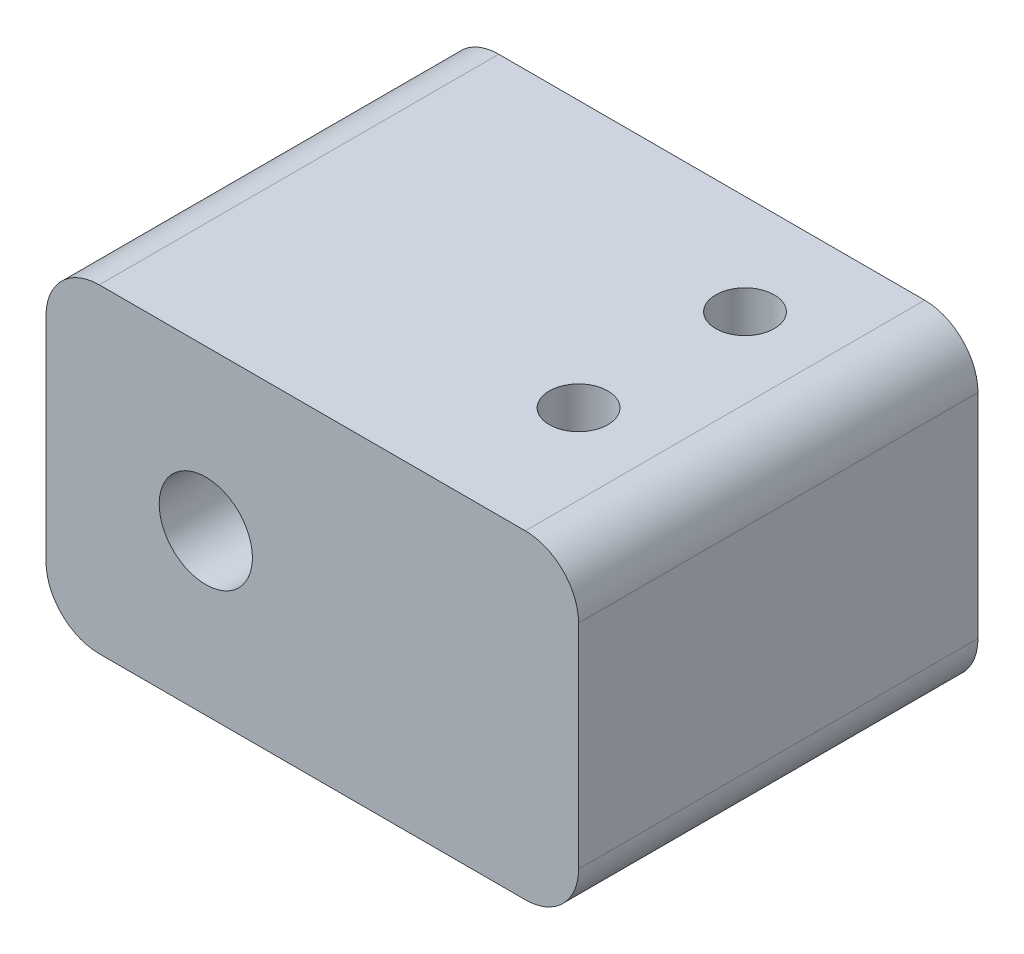
SolidWorks part; units mm, degrees
ref_plane "Front Plane" through (0, 0, 0) normal (0, 0, 1) x (1, 0, 0)
ref_plane "Top Plane" through (0, 0, 0) normal (0, 1, 0) x (1, 0, 0)
ref_plane "Right Plane" through (0, 0, 0) normal (1, 0, 0) x (0, 0, -1)
sketch "Sketch1" plane through (0, 0, 0) normal (0, 0, 1) x (1, 0, 0)
  circle A0 centre (0, 0) radius 1.25
  circle A1 centre (0, 0) radius 4.5
  dimension "D1" = 2.5
  dimension "D2" = 9
extrude "Boss-Extrude1" add sketch "Sketch1" along normal blind 8
sketch "Sketch2" plane through (0, 0, 0) normal (0, 0, -1) x (-1, 0, 0)
  circle A0 centre (0, 0) radius 1.25 construction
  circle A1 centre (0, 0) radius 4.5
  circle A2 centre (0, 0) radius 4.5
  circle A3 centre (0, 0) radius 1.25
  circle A4 centre (0, 0) radius 1.75
  circle M3 centre (0, 0) radius 1.25
  dimension "D2" = 3.5
  dimension "D1" = 0
extrude "Cut-Extrude1" cut sketch "Sketch2" against normal blind 4 contours A4 M3 region at (1.7005, 0, 0)
sketch "Sketch4" plane through (0, 0, 0) normal (0, 0, -1) x (-1, 0, 0)
  line L1 (3.25, -3.25) -> (-3.25, -3.25)
  line L2 (3.25, -3.25) -> (3.25, 3.25)
  line L3 (3.25, 3.25) -> (-3.25, 3.25)
  line L4 (-3.25, -3.25) -> (-3.25, 3.25)
  line L5 (0, 3.25) -> (0, -3.25) construction
  line L6 (3.25, 0) -> (-3.25, 0) construction
  line L7 (6, -6) -> (-6, -6)
  line L8 (6, -6) -> (6, 6)
  line L9 (6, 6) -> (-6, 6)
  line L10 (-6, -6) -> (-6, 6)
  line L11 (0, 6) -> (0, -6) construction
  line L12 (6, 0) -> (-6, 0) construction
  point P0 (0, 0)
  point P4 (0, 0)
  circle M5 centre (0, 0) radius 1.75
  circle M6 centre (0, 0) radius 4.5
  dimension "D1" = 6.5
  dimension "D2" = 6.5
  dimension "D3" = 12
  dimension "D4" = 12
extrude "Boss-Extrude2" add sketch "Sketch4" along normal blind 15
sketch "Sketch5" plane through (6, 0, 0) normal (1, 0, 0) x (0, 0, -1)
  line L4 (0, 6) -> (0, -6)
  line L5 (0, -6) -> (15, -6)
  line L6 (15, -6) -> (15, 6)
  line L7 (15, 6) -> (0, 6)
  line L8 (0, 6) -> (0, -6)
  line L9 (0, -6) -> (15, -6)
  line L10 (15, -6) -> (15, 6)
  line L11 (15, 6) -> (0, 6)
  dimension "D1" = 0
extrude "Boss-Extrude3" add sketch "Sketch5" along normal blind 8
sketch "Sketch6" plane through (0, 6, 0) normal (0, 1, 0) x (1, 0, 0)
  line L0 (4, 15) -> (4, 0) construction
  line L1 (4, 0) -> (14, 15) construction
  line L2 (9, 7.5) -> (9, 15) construction
  line L3 (9, 15) -> (9, 0) construction
  line L4 (-6, 0) -> (14, 0)
  line L5 (14, 0) -> (14, 15)
  line L6 (14, 15) -> (-6, 15)
  line L7 (-6, 15) -> (-6, 0)
  line L8 (-6, 0) -> (14, 0)
  line L9 (14, 0) -> (14, 15)
  line L10 (14, 15) -> (-6, 15)
  line L11 (-6, 15) -> (-6, 0)
  circle A0 centre (9, 11.25) radius 1.1
  circle A1 centre (9, 5) radius 1.1
  dimension "D2" = 2.2
  dimension "D3" = 2.2
  dimension "D4" = 5
  dimension "D1" = 0
extrude "Cut-Extrude2" cut sketch "Sketch6" against normal through all both and the other way through all contours A0 | A1
fillet "Fillet1" radius 2 4 edges at (-6, 6, -7.5) (-6, -6, -7.5) (14, -6, -7.5) (14, 6, -7.5)
extrude "Cut-Extrude5" cut sketch "Sketch1<2>" against normal blind 8 from surface starting at face at (4.5, 0, 8)
sketch "Sketch1<2>" plane through (0, 0, 0) normal (0, 0, 1) x (1, 0, 0) same geometry as "Sketch1"
extrude "Boss-Extrude5" add sketch "Sketch4<4>" along normal blind 3 contours L4 L1 L2 L3 M6 M5 | L4 L1 M6 | L4 L3 M6 | L2 L3 M6 | L1 L2 M6 region at (-3.2045, -3.2045, 0) region at (0, -3.1581, 0) region at (3.2045, -3.2045, 0) region at (-3.2045, 3.2045, 0) region at (3.2045, 3.2045, 0)
sketch "Sketch4<4>" plane through (0, 0, 0) normal (0, 0, -1) x (-1, 0, 0) same geometry as "Sketch4"
